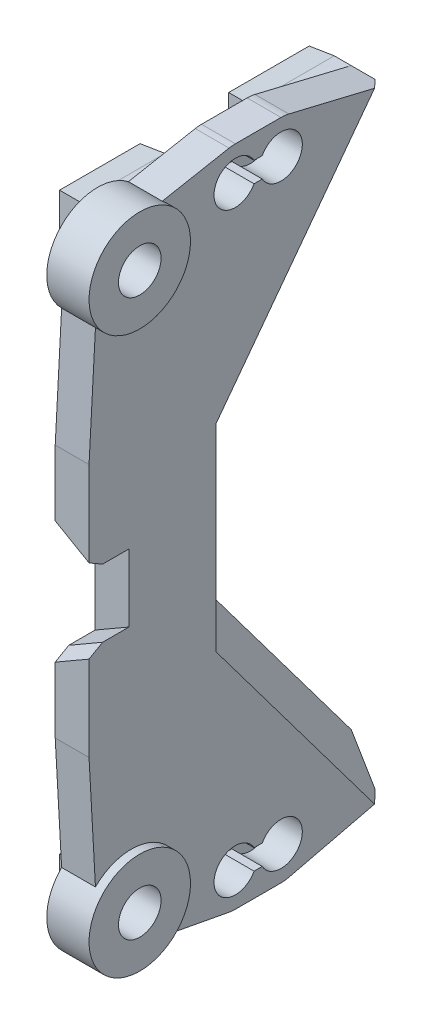
SolidWorks part; units mm, degrees
note: The reader was unsure of these and kept them because the rebuilt part matched: shared geometry of "Sketch11<2>".
ref_plane "Front Plane" through (0, 0, 0) normal (0, 0, 1) x (1, 0, 0)
ref_plane "Top Plane" through (0, 0, 0) normal (0, 1, 0) x (1, 0, 0)
ref_plane "Right Plane" through (0, 0, 0) normal (1, 0, 0) x (0, 0, -1)
sketch "SlideGeometry"
  dimension "D2" = 12.7
  dimension "D4" = 63.5
  dimension "D6" = 12.7
  dimension "D7" = 6.35
  dimension "D8" = 6.35
  dimension "D9" = 12.7
  dimension "D12" = 3.81
  dimension "D5" = 9.525
  dimension "D10" = 12.7
  dimension "D11" = 3.81
sketch_block_instance "PulleyOutline-1"
sketch_block "PulleyOutline" parameters "D1"=11.1125, "D2"=13.6525
sketch_block_instance "PulleyOutline-2"
sketch_block_instance "PulleyOutline-3"
sketch_block_instance "PulleyOutline-4"
sketch_block_instance "PulleyOutline-5"
sketch_block_instance "PulleyOutline-6"
sketch_block_instance "SlotOutline-1"
sketch_block "SlotOutline" parameters "D1"=6.35, "D2"=3
sketch_block_instance "SlotOutline-3"
sketch_block_instance "SlotOutline-4"
sketch "Sketch3" plane through (0, 0, 0) normal (1, 0, 0) x (0, 0, -1)
  circle A0 centre (-3.175, 20.8837) radius 3.81
  circle A1 centre (-3.175, 20.8837) radius 1.5 construction
  dimension "D1" = 7.62
  dimension "D2" = 3
extrude "DowelSupport" add sketch "Sketch3" along normal blind 1.905 and the other way blind 1.27
sketch "Sketch5" plane through (0, 0, 0) normal (1, 0, 0) x (0, 0, -1)
  line L1 (-6.35, -9.525) -> (3.175, -9.525)
  line L2 (-6.35, -9.525) -> (-6.35, 9.525)
  line L3 (-6.35, 9.525) -> (3.175, 9.525)
  line L4 (3.175, -9.525) -> (3.175, 9.525)
  line L5 (-6.35, -9.525) -> (3.175, 9.525) construction
  line L6 (-6.35, 9.525) -> (3.175, -9.525) construction
  point P0 (-1.5875, 0)
  dimension "D1" = 9.525
  dimension "D2" = 19.05
extrude "SliderDowelSupport" add sketch "Sketch5" along normal mid plane 2.54 separate body contours L3 L4 L1 L2
sketch "Sketch8" plane through (0, 0, 0) normal (1, 0, 0) x (0, 0, -1)
  line L0 (4.6355, 22.352) -> (8.0645, 22.352) construction
  line L1 (4.6355, 24.892) -> (8.0645, 24.892)
  line L2 (4.6355, 19.812) -> (8.0645, 19.812)
  line L3 (6.35, 25.4) -> (-6.35, 25.4) construction
  circle A0 centre (4.6355, 22.352) radius 1.5 construction
  circle A1 centre (8.0645, 22.352) radius 1.5 construction
  arc A2 (4.6355, 24.892) -> (4.6355, 19.812) centre (4.6355, 22.352) ccw
  arc A3 (5.7373, 23.3698) -> (5.5245, 22.352) centre (8.0645, 22.352) ccw construction
  arc A4 (8.0645, 24.892) -> (6.35, 24.2261) centre (8.0645, 22.352) ccw construction
  arc A5 (6.35, 24.2261) -> (4.6355, 24.892) centre (4.6355, 22.352) ccw construction
  arc A6 (6.35, 24.2261) -> (5.7373, 23.3698) centre (8.0645, 22.352) ccw construction
  arc A7 (6.9627, 23.3698) -> (6.35, 24.2261) centre (4.6355, 22.352) ccw construction
  arc A8 (7.1755, 22.352) -> (6.9627, 23.3698) centre (4.6355, 22.352) ccw construction
  arc A9 (6.9627, 21.3342) -> (7.1755, 22.352) centre (4.6355, 22.352) ccw construction
  arc A10 (6.35, 20.4779) -> (6.9627, 21.3342) centre (4.6355, 22.352) ccw construction
  arc A11 (5.7373, 21.3342) -> (6.35, 20.4779) centre (8.0645, 22.352) ccw construction
  arc A12 (8.0645, 19.812) -> (8.0645, 24.892) centre (8.0645, 22.352) ccw
  arc A13 (4.6355, 19.812) -> (6.35, 20.4779) centre (4.6355, 22.352) ccw construction
  arc A14 (6.35, 20.4779) -> (8.0645, 19.812) centre (8.0645, 22.352) ccw construction
  arc A15 (5.5245, 22.352) -> (5.7373, 21.3342) centre (8.0645, 22.352) ccw construction
  point P11 (6.35, 22.352)
  dimension "D1" = 3
  dimension "D3" = 5.08
  dimension "D2" = 3.429
  dimension "D4" = 0.508
  dimension "D5" = 9.525
extrude "StringDowelSupport" add sketch "Sketch8" along normal mid plane 2.54 separate body
sketch "Sketch9" plane through (0, 0, 0) normal (1, 0, 0) x (0, 0, -1)
  line B0 (3.175, 20.09) -> (-3.175, 20.09)
  line B1 (3.175, 20.09) -> (3.175, 23.09)
  line B2 (3.175, 23.09) -> (-3.175, 23.09)
  line B3 (-3.175, 20.09) -> (-3.175, 23.09)
  line B4 (3.175, 20.09) -> (-3.175, 23.09) construction
  line B5 (3.175, 23.09) -> (-3.175, 20.09) construction
  line B6 (15.875, 20.09) -> (9.525, 20.09)
  line B7 (15.875, 20.09) -> (15.875, 23.09)
  line B8 (15.875, 23.09) -> (9.525, 23.09)
  line B9 (9.525, 20.09) -> (9.525, 23.09)
sketch_block_instance "3DPTabGeo-1"
sketch_block "3DPTabGeo" parameters "D1"=3, "D2"=6.35
sketch_block_instance "3DPTabGeo-2"
extrude "TabSupport" add sketch "Sketch9" along normal mid plane 2.54
sketch "Sketch10" plane through (0, 0, 0) normal (1, 0, 0) x (0, 0, -1)
  line L0 (-6.35, 9.525) -> (-5.7111, 21.0247)
  line L1 (-5.7111, 21.0247) -> (-0.6389, 20.7428) construction
  line L2 (-6.35, 9.525) -> (3.175, 9.525)
  line L3 (3.175, 9.525) -> (3.175, 3.175)
  line L4 (3.175, 3.175) -> (15.875, 20.09)
  line L5 (15.875, 20.09) -> (15.875, 23.09)
  line L6 (15.875, 23.09) -> (8.6571, 24.8219)
  line L7 (8.6571, 24.8219) -> (4.1662, 24.8483)
  line L8 (4.1662, 24.8483) -> (-3.6443, 23.38)
  line L9 (-3.6443, 23.38) -> (-2.7057, 18.3875) construction
  line L10 (-5.7111, 21.0247) -> (-3.6443, 23.38)
  line L11 (3.175, -9.525) -> (3.175, 9.525) construction
  arc A0 (4.6355, 24.892) -> (4.6355, 19.812) centre (4.6355, 22.352) ccw construction
  arc A1 (8.0645, 19.812) -> (8.0645, 24.892) centre (8.0645, 22.352) ccw construction
  point P3 (-3.175, 20.8837)
  dimension "D1" = 5.08
  dimension "D2" = 6.35
extrude "InterSupport" add sketch "Sketch10" along normal mid plane 2.54
sketch "Sketch11" plane through (0, 0, 0) normal (1, 0, 0) x (0, 0, -1)
  line L1 (6.0424, 21.59) -> (6.6576, 21.59)
  line L2 (6.0424, 21.59) -> (6.0424, 23.114) construction
  line L3 (6.0424, 23.114) -> (6.6576, 23.114)
  line L4 (6.6576, 21.59) -> (6.6576, 23.114) construction
  line L5 (6.0424, 21.59) -> (6.6576, 23.114) construction
  line L6 (6.0424, 23.114) -> (6.6576, 21.59) construction
  circle A0 centre (-3.175, 20.8837) radius 1.6
  arc A1 (6.0424, 23.114) -> (6.0424, 21.59) centre (4.6355, 22.352) ccw
  arc A2 (6.6576, 21.59) -> (6.6576, 23.114) centre (8.0645, 22.352) ccw
  arc A3 (6.1771, 22.7803) -> (6.0424, 23.114) centre (4.6355, 22.352) ccw construction
  arc A4 (6.6576, 23.114) -> (6.5229, 22.7803) centre (8.0645, 22.352) ccw construction
  arc A5 (6.5229, 22.7803) -> (6.5229, 21.9237) centre (8.0645, 22.352) ccw construction
  arc A6 (6.1771, 21.9237) -> (6.1771, 22.7803) centre (4.6355, 22.352) ccw construction
  arc A7 (6.0424, 21.59) -> (6.1771, 21.9237) centre (4.6355, 22.352) ccw construction
  arc A8 (6.5229, 21.9237) -> (6.6576, 21.59) centre (8.0645, 22.352) ccw construction
  point P9 (6.35, 22.352)
  dimension "D1" = 3.2
  dimension "D3" = 1.524
extrude "DowelHoles" cut sketch "Sketch11" against normal through all both and the other way through all
extrude "Boss-Extrude1" add sketch "Sketch11<2>" along normal blind 0.254 from surface contours L1 A2 L3 A1 | A0
sketch "Sketch11<2>" plane through (0, 0, 0) normal (1, 0, 0) x (0, 0, -1) same geometry as "Sketch11"
sketch "Sketch14" plane through (-1.27, 0, 0) normal (-1, 0, 0) x (0, 0, 1)
  line B0 (-9.525, 20.09) -> (-15.875, 20.09)
  line B1 (-9.525, 20.09) -> (-9.525, 23.09)
  line B2 (-9.525, 23.09) -> (-15.875, 23.09)
  line B3 (-15.875, 20.09) -> (-15.875, 23.09)
  line B4 (-9.525, 23.09) -> (-15.875, 20.09) construction
  line B5 (3.175, 20.09) -> (-3.175, 20.09)
  line B6 (3.175, 20.09) -> (3.175, 23.09)
  line B7 (3.175, 23.09) -> (-3.175, 23.09)
  line B8 (-3.175, 20.09) -> (-3.175, 23.09)
sketch_block_instance "3DPTabGeo-3"
sketch_block_instance "3DPTabGeo-4"
extrude "TabBase" add sketch "Sketch14" along normal blind 1.27
sketch "Sketch15" plane through (-2.54, 0, 0) normal (-1, 0, 0) x (0, 0, 1)
  line L0 (-3.175, 23.09) -> (-3.175, 20.09) construction
  line L1 (-3.175, 20.09) -> (3.175, 20.09) construction
  line L2 (3.175, 20.09) -> (3.175, 23.09) construction
  line L3 (3.175, 23.09) -> (-3.175, 23.09) construction
  line L4 (-15.875, 23.09) -> (-15.875, 20.09) construction
  line L5 (-15.875, 20.09) -> (-9.525, 20.09) construction
  line L6 (-9.525, 20.09) -> (-9.525, 23.09) construction
  line L7 (-9.525, 23.09) -> (-15.875, 23.09) construction
  line L8 (-3.175, 23.09) -> (-3.175, 20.09)
  line L9 (-3.175, 20.09) -> (3.175, 20.09)
  line L10 (3.175, 20.09) -> (3.175, 23.09)
  line L11 (3.175, 23.09) -> (-3.175, 23.09)
  line L12 (-15.875, 23.09) -> (-15.875, 20.09)
  line L13 (-15.875, 20.09) -> (-9.525, 20.09)
  line L14 (-9.525, 20.09) -> (-9.525, 23.09)
  line L15 (-9.525, 23.09) -> (-15.875, 23.09)
extrude "TabDraft" add sketch "Sketch15" along normal offset from surface 3 draft 5
chamfer "Chamfer1" distance 2.54 angle 45 1 edges at (1.27, 11.6325, -9.525)
mirror "Mirror1" about plane through (0, 0, 0) normal (0, 1, 0) of bodies 118 115
sketch "Sketch16" plane through (0, 0, 6.35) normal (0, 0, 1) x (1, 0, 0)
  line L0 (-1.27, -4.0065) -> (1.27, -2.54)
  line L1 (-1.27, -9.525) -> (-1.27, 9.525) construction
  line L2 (1.27, -9.525) -> (1.27, 9.525) construction
  line L3 (1.27, -2.54) -> (1.27, 2.54)
  line L4 (1.27, 2.54) -> (-1.27, 4.0065)
  line L5 (-1.27, 4.0065) -> (-1.27, -4.0065)
  line L6 (0, 0) -> (5.5741, 0) construction
  dimension "D1" = 5.08
  dimension "D2" = 60
extrude "Cut-Extrude1" cut sketch "Sketch16" against normal blind 3
chamfer "Chamfer2" distance 0.508 distance2 1.016 2 edges at (0, -3.2732, 6.35) (0, 3.2732, 6.35)
equation "\"StageWidth\"= 2in"
equation "\"D1@SlideGeometry\" = \"StageWidth\""
equation "\"StageOffset\"= .5in"
equation "\"D3@SlideGeometry\" = \"StageWidth\" - \"StageOffset\""
equation "\"D4@SlideGeometry\" = \"StageWidth\" + \"StageOffset\""
equation "\"SlideOffset\"= 0.5in"
equation "\"D6@SlideGeometry\" = \"SlideOffset\""
equation "\"D7@SlideGeometry\" = \"StageOffset\" / 2"
equation "\"D8@SlideGeometry\" = \"StageOffset\" / 2"
equation "\"D9@SlideGeometry\" = \"SlideOffset\""
equation "\"OuterThickness\"= 0.1in"
equation "\"D1@SliderDowelSupport\"=\"OuterThickness\""
equation "\"D1@DowelSupport\"=\"OuterThickness\"/2+.025"
equation "\"DowelClearance\"= 3mm + .2mm"
equation "\"D1@TabSupport\" = \"OuterThickness\""
equation "\"D1@InterSupport\" = \"OuterThickness\""
equation "\"D1@Sketch11\"=\"DowelClearance\""
equation "\"D2@Sketch11\"=\"DowelClearance\""
equation "\"SliderDowelLength\"= .5in"
equation "\"D2@Sketch5\"=\"SliderDowelLength\"+.25in"
equation "\"D11@SlideGeometry\"=\"D12@SlideGeometry\""
equation "\"D2@DowelSupport\"=\"OuterThickness\"/2"
